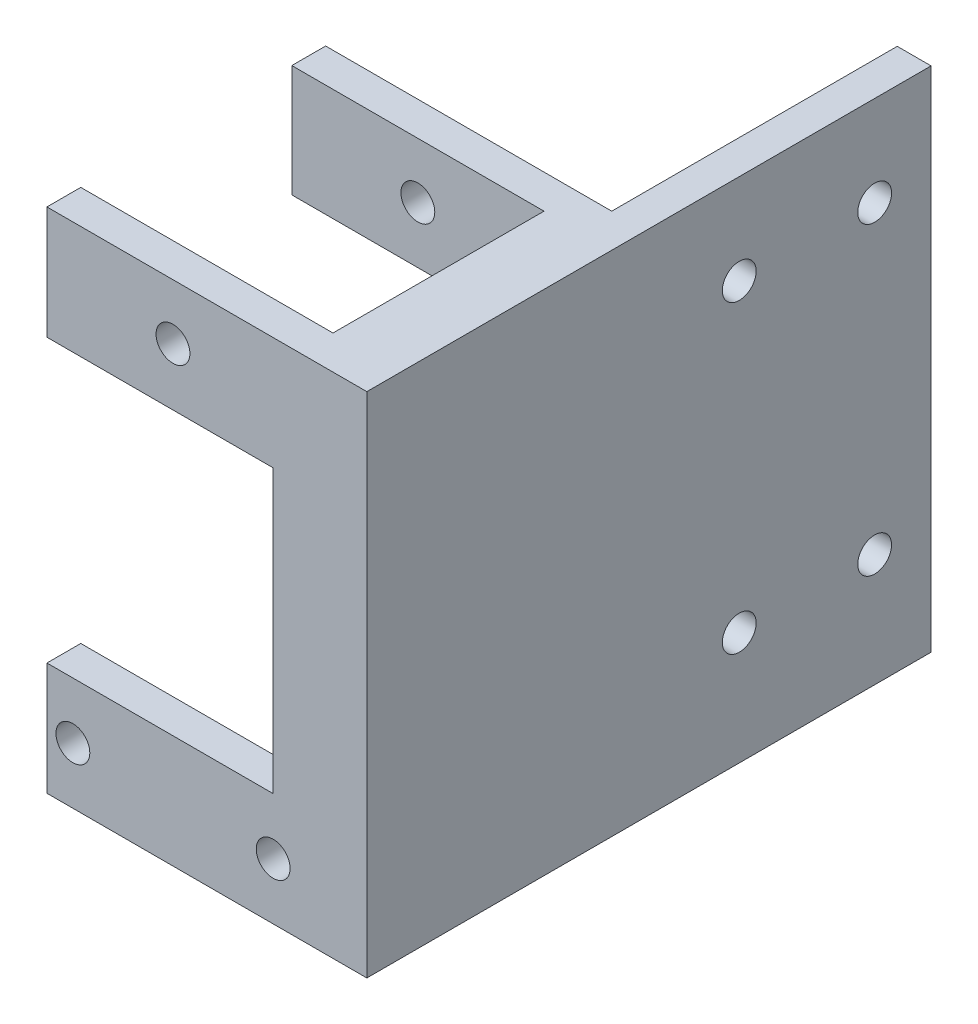
SolidWorks part; units mm, degrees
note: The reader was unsure of these and kept them because the rebuilt part matched: shared geometry of "Sketch8<3>".
ref_plane "Front Plane" through (0, 0, 0) normal (0, 0, 1) x (1, 0, 0)
ref_plane "Top Plane" through (0, 0, 0) normal (0, 1, 0) x (1, 0, 0)
ref_plane "Right Plane" through (0, 0, 0) normal (1, 0, 0) x (0, 0, -1)
sketch "Sketch2" plane through (0, 0, 0) normal (0, 0, 1) x (1, 0, 0)
  line L1 (12.675, -22.5) -> (-12.675, -22.5)
  line L2 (12.675, -22.5) -> (12.675, 22.5)
  line L3 (12.675, 22.5) -> (-12.675, 22.5)
  line L4 (-12.675, -22.5) -> (-12.675, 22.5)
  line L5 (12.675, -22.5) -> (-12.675, 22.5) construction
  line L6 (12.675, 22.5) -> (-12.675, -22.5) construction
  line L7 (-12.675, 22.5) -> (12.675, 22.5)
  line L8 (-12.675, 22.5) -> (-12.675, 12.5)
  line L9 (-12.675, 12.5) -> (12.675, 12.5)
  line L10 (12.675, 22.5) -> (12.675, 12.5)
  line L11 (-12.675, -22.5) -> (12.675, -22.5)
  line L12 (-12.675, -22.5) -> (-12.675, -12.5)
  line L13 (-12.675, -12.5) -> (12.675, -12.5)
  line L14 (12.675, -22.5) -> (12.675, -12.5)
  line L15 (12.675, 12.5) -> (7.375, 12.5)
  line L16 (12.675, 12.5) -> (12.675, -12.5)
  line L17 (12.675, -12.5) -> (7.375, -12.5)
  line L18 (7.375, 12.5) -> (7.375, -12.5)
  line L19 (-12.675, 12.5) -> (7.375, 12.5)
  line L20 (-12.675, 12.5) -> (-12.675, -12.5)
  line L21 (-12.675, -12.5) -> (7.375, -12.5)
  line L22 (7.375, 12.5) -> (7.375, -12.5)
  circle A0 centre (-1.505, 17.58) radius 1.5
  circle A2 centre (7.375, -17.5) radius 1.5
  circle A4 centre (-10.375, -17.5) radius 1.5
  point P0 (0, 0)
  dimension "D5" = 8.88
  dimension "D6" = 35.08
  dimension "D7" = 20.05
  dimension "D10" = 3
  dimension "D11" = 2.3
  dimension "D12" = 5
  dimension "D13" = 3
  dimension "D15" = 5
  dimension "D16" = 3
  dimension "D1" = 25.35
  dimension "D2" = 45
  dimension "D3" = 10
  dimension "D4" = 10
  dimension "D14" = 17.75
extrude "Boss-Extrude1" add sketch "Sketch2" against normal blind 3 contours L9 L18 L13 L2 | L4 L9 L2 L3 A0 | L13 L4 L1 L2 A4 A2
sketch "Sketch3" plane through (12.675, 0, 0) normal (1, 0, 0) x (0, 0, -1)
  line L1 (0, 22.5) -> (50, 22.5)
  line L2 (0, 22.5) -> (0, -22.5)
  line L3 (0, -22.5) -> (50, -22.5)
  line L4 (50, 22.5) -> (50, -22.5)
  dimension "D1" = 50
  dimension "D2" = 45
extrude "Boss-Extrude2" add sketch "Sketch3" along normal blind 3
sketch "Sketch7" plane through (0, 22.5, 0) normal (0, 1, 0) x (1, 0, 0)
  line L0 (15.675, 50) -> (15.675, 0) construction
  line L1 (15.675, 24.7) -> (-22.675, 24.7)
  line L2 (15.675, 24.7) -> (15.675, 21.7)
  line L3 (15.675, 21.7) -> (-22.675, 21.7)
  line L4 (-22.675, 24.7) -> (-22.675, 21.7)
  line L5 (12.675, 3) -> (-12.675, 3) construction
  dimension "D1" = 18.7
  dimension "D2" = 3
  dimension "D3" = 38.35
extrude "Boss-Extrude3" add sketch "Sketch7" against normal blind 45
sketch "Sketch8" plane through (0, 0, -21.7) normal (0, 0, 1) x (1, 0, 0)
  line L0 (15.675, 22.5) -> (15.675, -22.5) construction
  line L1 (-12.675, 22.5) -> (15.675, 22.5)
  line L2 (-12.675, 22.5) -> (-12.675, 12.5728)
  line L3 (-12.675, 12.5728) -> (15.675, 12.5728)
  line L4 (15.675, 22.5) -> (15.675, 12.5728)
  line L6 (-12.675, -12.5) -> (15.675, -12.5)
  line L7 (-12.675, -12.5) -> (-12.675, -22.5)
  line L8 (-12.675, -22.5) -> (15.675, -22.5)
  line L9 (15.675, -12.5) -> (15.675, -22.5)
  line L10 (7.375, -12.5) -> (15.675, -12.5)
  line L11 (7.375, -12.5) -> (7.375, 12.5728)
  line L12 (7.375, 12.5728) -> (15.675, 12.5728)
  line L13 (15.675, -12.5) -> (15.675, 12.5728)
  circle A0 centre (-1.505, 17.58) radius 1.5
  circle A1 centre (-10.375, -17.5) radius 1.5
  circle A2 centre (7.375, -17.5) radius 1.5
  line M3 (-22.675, 22.5) -> (-22.675, -22.5)
  dimension "D1" = 3
  dimension "D4" = 3
  dimension "D5" = 3
  dimension "D2" = 5.0072
  dimension "D3" = 17.75
extrude "Cut-Extrude1" cut sketch "Sketch8" against normal blind 5 contours L6 L11 L3 M3
extrude "Cut-Extrude2" cut sketch "Sketch8<3>" against normal blind 5 contours A0 | A2 | A1 | L6 L11 L3 M3
sketch "Sketch8<3>" plane through (0, 0, -21.7) normal (0, 0, 1) x (1, 0, 0) same geometry as "Sketch8"
sketch "Sketch11" plane through (15.675, 0, 0) normal (1, 0, 0) x (0, 0, -1)
  line L0 (0, -22.5) -> (50, -22.5) construction
  line L8 (50, -22.5) -> (50, 22.5) construction
  line L11 (50, 22.5) -> (0, 22.5) construction
  circle A4 centre (33, 14.5) radius 1.5
  circle A5 centre (45, 14.5) radius 1.5
  circle A6 centre (33, -12.5) radius 1.5
  circle A7 centre (45, -12.5) radius 1.5
  dimension "D2" = 5
  dimension "D3" = 8
  dimension "D4" = 27
  dimension "D5" = 5
  dimension "D7" = 3
  dimension "D6" = 8
  dimension "D8" = 3
  dimension "D9" = 3
  dimension "D10" = 3
  dimension "D11" = 12
  dimension "D12" = 12
  dimension "D13" = 10
extrude "Cut-Extrude4" cut sketch "Sketch11" against normal blind 5
sketch "Sketch12" plane through (12.675, 0, 0) normal (-1, 0, 0) x (0, 0, 1)
  line L1 (-21.7, 22.5) -> (-3, 22.5)
  line L2 (-21.7, 22.5) -> (-21.7, -22.5)
  line L3 (-21.7, -22.5) -> (-3, -22.5)
  line L4 (-3, 22.5) -> (-3, -22.5)
extrude "Boss-Extrude4" add sketch "Sketch12" along normal blind 3
